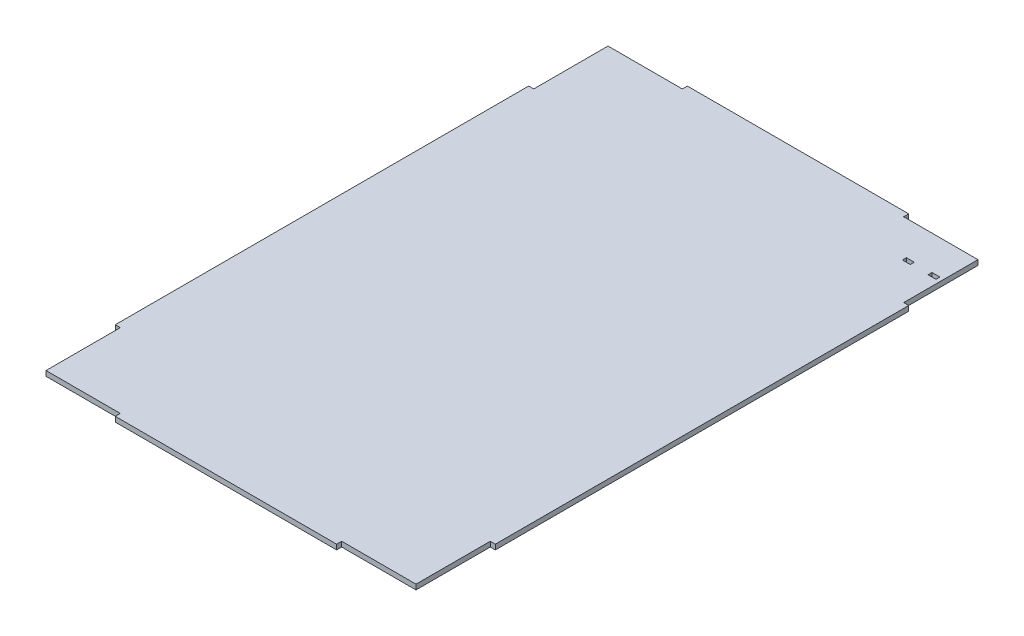
SolidWorks part; units mm, degrees
ref_plane "Front Plane" through (0, 0, 0) normal (0, 0, 1) x (1, 0, 0)
ref_plane "Top Plane" through (0, 0, 0) normal (0, 1, 0) x (1, 0, 0)
ref_plane "Right Plane" through (0, 0, 0) normal (1, 0, 0) x (0, 0, -1)
sketch "Sketch1" plane through (0, 0, 0) normal (0, 1, 0) x (1, 0, 0)
  line L7 (-239.5, -360.5) -> (239.5, -360.5)
  line L8 (-239.5, -360.5) -> (-239.5, 360.5)
  line L9 (-239.5, 360.5) -> (239.5, 360.5)
  line L10 (239.5, -360.5) -> (239.5, 360.5)
  point P0 (0, 0)
  point P3 (239.5, 0)
  point P6 (0, 0)
  point P11 (0, -360.5)
  dimension "D1" = 721
  dimension "D2" = 479
extrude "Boss-Extrude1" add sketch "Sketch1" along normal mid plane 6.35
sketch "Sketch2" plane through (0, 3.175, 0) normal (0, 1, 0) x (1, 0, 0)
  line L0 (-239.5, 360.5) -> (-239.5, 260.5)
  line L1 (-239.5, 360.5) -> (-239.5, -360.5) construction
  line L2 (-239.5, 260.5) -> (-233.15, 260.5)
  line L3 (-233.15, 260.5) -> (-233.15, 354.15)
  line L4 (-233.15, 354.15) -> (-139.5, 354.15)
  line L5 (-139.5, 354.15) -> (-139.5, 360.5)
  line L6 (239.5, 360.5) -> (-239.5, 360.5) construction
  line L7 (-139.5, 360.5) -> (-239.5, 360.5)
  line L8 (239.5, 360.5) -> (139.5, 360.5)
  line L9 (139.5, 360.5) -> (139.5, 354.15)
  line L10 (139.5, 354.15) -> (233.15, 354.15)
  line L11 (233.15, 354.15) -> (233.15, 260.5)
  line L12 (233.15, 260.5) -> (239.5, 260.5)
  line L13 (239.5, -360.5) -> (239.5, 360.5) construction
  line L14 (239.5, 260.5) -> (239.5, 360.5)
  line L15 (239.5, -360.5) -> (239.5, -260.5)
  line L16 (239.5, -260.5) -> (233.15, -260.5)
  line L17 (233.15, -260.5) -> (233.15, -354.15)
  line L18 (233.15, -354.15) -> (139.5, -354.15)
  line L19 (139.5, -354.15) -> (139.5, -360.5)
  line L20 (-239.5, -360.5) -> (239.5, -360.5) construction
  line L21 (139.5, -360.5) -> (239.5, -360.5)
  line L22 (-239.5, -360.5) -> (-139.5, -360.5)
  line L23 (-139.5, -360.5) -> (-139.5, -354.15)
  line L24 (-139.5, -354.15) -> (-233.15, -354.15)
  line L25 (-233.15, -354.15) -> (-233.15, -260.5)
  line L26 (-233.15, -260.5) -> (-239.5, -260.5)
  line L27 (-239.5, -260.5) -> (-239.5, -360.5)
  dimension "D1" = 100
  dimension "D2" = 6.35
extrude "Cut-Extrude1" cut sketch "Sketch2" against normal through all
sketch "Sketch3" plane through (0, -3.175, 0) normal (0, -1, 0) x (1, 0, 0)
  line L0 (233.15, -354.15) -> (233.15, -260.5) construction
  line L1 (139.5, -354.15) -> (233.15, -354.15) construction
  line L8 (185.85, -306.15) -> (195.85, -306.15)
  line L9 (185.85, -306.15) -> (185.85, -311.15)
  line L10 (185.85, -311.15) -> (195.85, -311.15)
  line L11 (195.85, -306.15) -> (195.85, -311.15)
  line L12 (228.15, -306.15) -> (228.15, -311.15)
  line L13 (218.15, -306.15) -> (228.15, -306.15)
  line L14 (218.15, -306.15) -> (218.15, -311.15)
  line L15 (218.15, -311.15) -> (228.15, -311.15)
  dimension "D1" = 10
  dimension "D2" = 5
  dimension "D3" = 5
  dimension "D4" = 42.3
  dimension "D5" = 43
extrude "Cut-Extrude2" cut sketch "Sketch3" against normal through all
